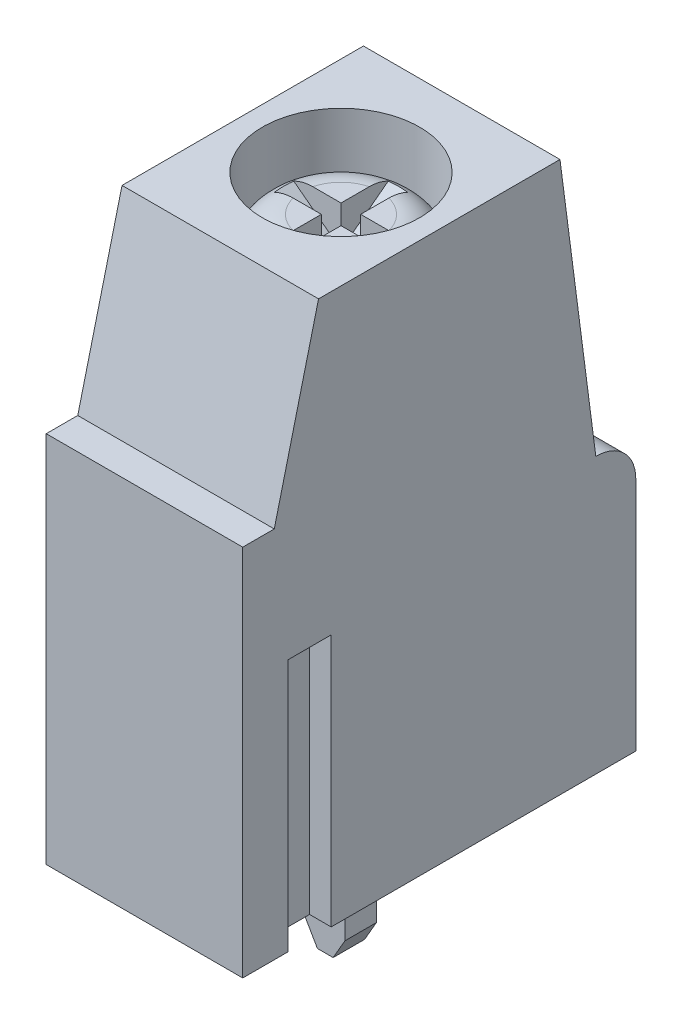
SolidWorks part; units mm, degrees
ref_plane "Plano frontal" through (0, 0, 0) normal (0, 0, 1) x (1, 0, 0)
ref_plane "Plano superior" through (0, 0, 0) normal (0, 1, 0) x (1, 0, 0)
ref_plane "Plano direito" through (0, 0, 0) normal (1, 0, 0) x (0, 0, -1)
sketch "Sketch1" plane through (0, 0, 0) normal (1, 0, 0) x (0, 0, -1)
  line L0 (10, 0) -> (10, 14) construction
  line L1 (0, 0) -> (0, 14) construction
  line L2 (10, 14) -> (0, 14) construction
  line L3 (8.0713, 14) -> (8.9833, 7)
  line L4 (8.0713, 14) -> (1.9287, 14)
  line L5 (10, 0) -> (0, 0)
  line L6 (8.9833, 7) -> (9, 7)
  line L7 (10, 6) -> (10, 0)
  line L8 (1.9287, 14) -> (0.8022, 9.4936)
  line L9 (0.8022, 9.4936) -> (0, 9.4936)
  line L10 (0, 9.4936) -> (0, 0)
  arc A0 (9, 7) -> (10, 6) centre (9, 6) cw
  point P10 (5, 14)
  dimension "D1" = 1
  dimension "D3" = 10
extrude "Boss-Extrude1" add sketch "Sketch1" along normal blind 5
ref_plane "Плоскость6" through (0.5, 0, 0) normal (-1, 0, 0) x (0, 0, 1)
sketch "Эскиз2" plane through (0.5, 0, 0) normal (-1, 0, 0) x (0, 0, 1)
  line L0 (-10, 5.692) -> (-8.6569, 5.0469)
  line L1 (-8.6569, 5.0469) -> (-2.9311, 5.0469)
  line L2 (-2.9311, 5.0469) -> (-2.9311, 0.9686)
  line L3 (-2.9311, 0.9686) -> (-8.4002, 0.9686)
  line L4 (-8.4002, 0.9686) -> (-10, 0.5424)
  line L5 (-10, 5.692) -> (-10, 0.5424)
  line L6 (-10, 0) -> (-10, 6) construction
  dimension "D1" = 0
extrude "Вырез-Вытянуть1" cut sketch "Эскиз2" against normal blind 4
sketch "Эскиз4" plane through (0, 14, 0) normal (0, 1, 0) x (1, 0, 0)
  line L0 (2.5, 1.9287) -> (2.5, 8.0713) construction
  line L1 (5, 1.9287) -> (0, 1.9287) construction
  line L2 (5, 8.0713) -> (0, 8.0713) construction
  circle A0 centre (2.5, 5) radius 2
  point P2 (2.5, 5)
  point P14 (2.5, 5.0443)
extrude "Вырез-Вытянуть2" cut sketch "Эскиз4" against normal blind 4 contours A0
ref_plane "Плоскость10" through (2.5, 0, 0) normal (-1, 0, 0) x (0, 0, 1)
sketch "Эскиз5" plane through (2.5, 0, 0) normal (-1, 0, 0) x (0, 0, 1)
  line L1 (-5, 13.0768) -> (-6, 13.0768)
  line L2 (-5, 13.0768) -> (-5, 11.3564)
  line L3 (-5, 11.3564) -> (-7, 11.3564)
  line L4 (-7, 12.0768) -> (-7, 11.3564)
  line L6 (0, 9.4936) -> (0, 0) construction
  arc A0 (-6, 13.0768) -> (-7, 12.0768) centre (-6, 12.0768) ccw
  point P6 (-7, 13.0768)
  dimension "D2" = 1
  dimension "D1" = 2
  dimension "D3" = 5
ref_plane "Плоскость11" through (0, 0, -5) normal (0, 0, -1) x (-1, 0, 0)
revolve "Повернуть1" add sketch "Эскиз5" angle 360 about L2
sketch "Эскиз6" plane through (2.5, 0, 0) normal (-1, 0, 0) x (0, 0, 1)
  line L4 (-6.7587, 13.1918) -> (-5, 13.1918)
  line L6 (-5.25, 12.0429) -> (-6.7587, 13.1918)
  line L8 (-5.25, 12.0429) -> (-5, 12.0429)
  line L9 (-5, 12.0429) -> (-5, 13.1918)
  line L10 (-5, 2.75) -> (-5, -2.75) construction
  point P1 (-5.0883, 13.1751)
  dimension "D1" = 0
  dimension "D2" = 0.25
extrude "Вырез-Вытянуть3" cut sketch "Эскиз6" against normal blind 0.5 from offset 0.25
ref_axis "Ось2" through (2.5, -0.7, -5) along (0, 1, 0)
pattern_circular "Круговой массив2" count 4 every 90 about axis through (2.5, -0.7, -5) along (0, 1, 0) of "Вырез-Вытянуть3"
sketch "Эскиз7" plane through (0, 0, 0) normal (-1, 0, 0) x (0, 0, 1)
  line L0 (0, 0) -> (-10, 0) construction
  line L1 (-2.2, 6.3856) -> (-1.2, 6.3856)
  line L2 (-2.2, 6.3856) -> (-2.2, 0)
  line L3 (-2.2, 0) -> (-1.2, 0)
  line L4 (-1.2, 6.3856) -> (-1.2, 0)
  line L6 (0, 9.4936) -> (0, 0) construction
  dimension "D1" = 1
  dimension "D2" = 1.2
extrude "Бобышка-Вытянуть1" add sketch "Эскиз7" along normal blind 0.5 contours L4 L3 L2 L1
sketch "Эскиз8" plane through (5, 0, 0) normal (1, 0, 0) x (0, 0, -1)
  line L0 (2.2, 6.3856) -> (2.2, 0) construction
  line L1 (1.15, 6.4356) -> (2.25, 6.4356)
  line L2 (1.15, 6.4356) -> (1.15, 0)
  line L3 (1.15, 0) -> (2.25, 0)
  line L4 (2.25, 6.4356) -> (2.25, 0)
  line L5 (1.2, 6.3856) -> (1.2, 0) construction
  line L6 (2.2, 6.3856) -> (1.2, 6.3856) construction
  dimension "D1" = 0.05
  dimension "D2" = 0.05
  dimension "D3" = 0.05
extrude "Вырез-Вытянуть4" cut sketch "Эскиз8" against normal blind 0.55
sketch "Эскиз10" plane through (0, 0, 0) normal (0, -1, 0) x (-1, 0, 0)
  line L1 (-3, 4.6) -> (-2, 4.6)
  line L2 (-3, 4.6) -> (-3, 5.4)
  line L3 (-3, 5.4) -> (-2, 5.4)
  line L4 (-2, 4.6) -> (-2, 5.4)
  line L5 (-3, 4.6) -> (-2, 5.4) construction
  line L6 (-3, 5.4) -> (-2, 4.6) construction
  point P0 (-2.5, 5)
  dimension "D1" = 1
  dimension "D2" = 0
  dimension "D3" = 0.8
extrude "Бобышка-Вытянуть2" add sketch "Эскиз10" along normal blind 3 contours L3 L4 L1 L2
chamfer "Фаска2" distance 0.3 angle 60 1 edges at (2, -3, -5) first distance on face at (2.5, -3, -5)
chamfer "Фаска3" distance 0.3 angle 60 1 edges at (3, -3, -5) first distance on face at (2.65, -3, -5)
